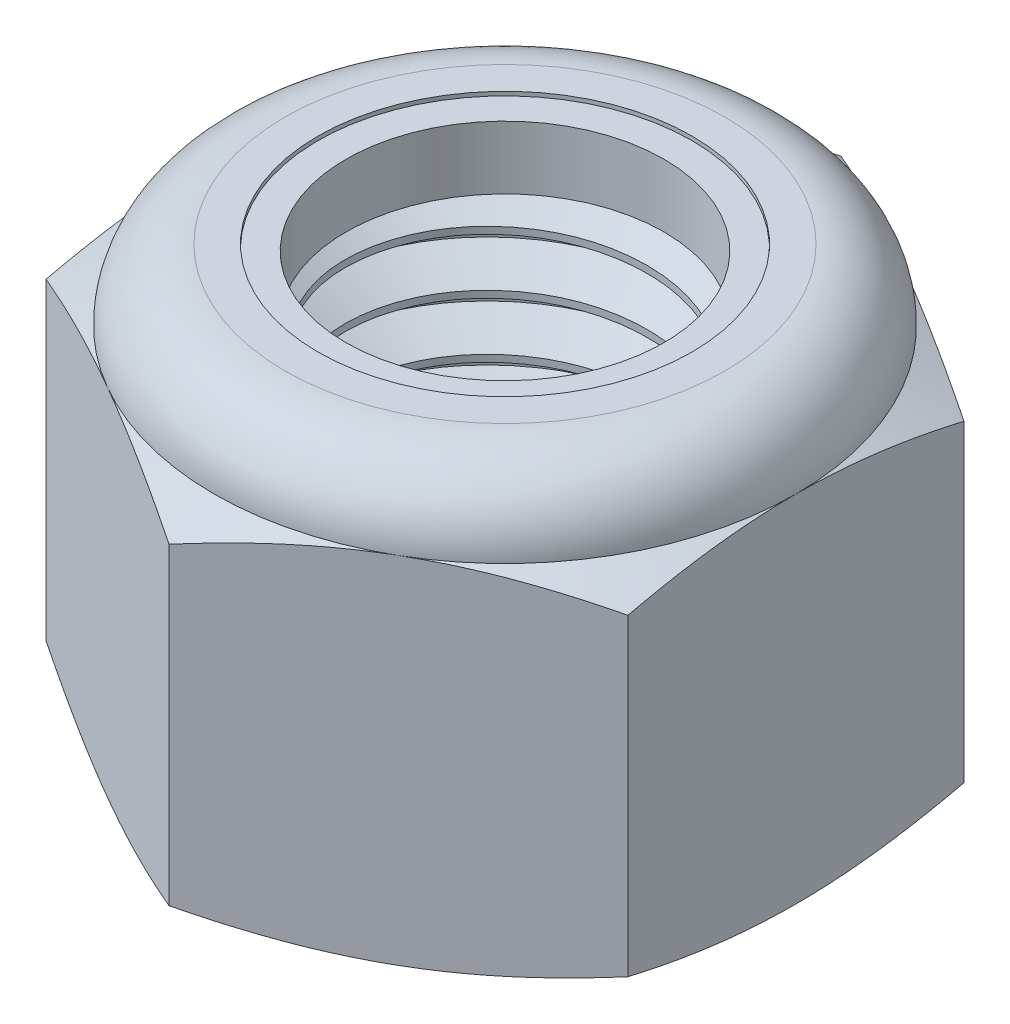
SolidWorks part; units mm, degrees
note: '?' marks a value the reader was unsure of.
material "Plain Carbon Steel"
ref_plane "Front" through (0, 0, 0) normal (0, 0, 1) x (1, 0, 0)
ref_plane "Top" through (0, 0, 0) normal (0, 1, 0) x (1, 0, 0)
ref_plane "Right" through (0, 0, 0) normal (1, 0, 0) x (0, 0, -1)
sketch "Sketch8" plane through (0, 0, 0) normal (1, 0, 0) x (0, 0, -1)
  line L0 (0, 0) -> (0, 16.2719) construction
  line L1 (11.1125, 0) -> (-11.1125, 0) construction
  line L2 (-7.1437, 16.2719) -> (7.1437, 16.2719) construction
  line L3 (7.1437, 16.2719) -> (7.1438, 14.1552) construction
sketch "Sketch1" plane through (0, 0, 0) normal (0, 1, 0) x (1, 0, 0)
  line L1 (0, 12.8316) -> (-11.1125, 6.4158)
  line L2 (-11.1125, 6.4158) -> (-11.1125, -6.4158)
  line L3 (-11.1125, -6.4158) -> (0, -12.8316)
  line L4 (0, -12.8316) -> (11.1125, -6.4158)
  line L5 (11.1125, -6.4158) -> (11.1125, 6.4158)
  line L6 (11.1125, 6.4158) -> (0, 12.8316)
  circle A0 centre (0, 0) radius 11.1125 construction
  circle A1 centre (0, 0) radius 7.1437
extrude "Extrude1" add sketch "Sketch1" along normal up to vertex (16.2719 mm away) up to point (0, 16.2719, 0)
sketch "Sketch5" plane through (0, 0, 0) normal (1, 0, 0) x (0, 0, -1)
  line L0 (0, 0) -> (11.1125, 0)
  line L1 (11.1125, 0) -> (12.8316, 0.8016)
  line L2 (12.8316, 0.8016) -> (12.8316, 12.7583)
  line L3 (12.8316, 12.7583) -> (11.1125, 13.5599)
  line L4 (8.4005, 16.2719) -> (8.4005, 17.5419)
  line L5 (8.4005, 17.5419) -> (14.1016, 17.5419)
  line L6 (14.1016, 17.5419) -> (14.1016, -1.27)
  line L7 (14.1016, -1.27) -> (0, -1.27)
  line L8 (0, -1.27) -> (0, 0)
  line L9 (11.1125, 13.5599) -> (11.1125, 0) construction
  line L12 (12.8316, 16.2719) -> (12.8316, 0) construction
  line L13 (12.8316, 8.1359) -> (14.1016, 8.1359) construction
  line L15 (0, 0) -> (0, 17.5419) construction
  line L18 (11.1125, 0) -> (-11.1125, 0) construction
  line L19 (6.4158, 16.2719) -> (12.8316, 16.2719) construction
  line L20 (0, 17.5419) -> (8.4005, 17.5419) construction
  line L21 (6.4158, 0) -> (12.8316, 0) construction
  arc A0 (11.1125, 13.5599) -> (8.4005, 16.2719) centre (8.4005, 13.5599) ccw
  dimension "D1" = 25
  dimension "D2" = 1.27
  dimension "D4" = 2.712
revolve "Cut-Revolve3" cut sketch "Sketch5" angle 360 about L15
sketch "Sketch4" plane through (0, 0, 0) normal (1, 0, 0) x (0, 0, -1)
  line L0 (0, 13.5599) -> (7.8581, 13.5599)
  line L1 (7.8581, 13.5599) -> (0, 9.8956)
  line L3 (0, 3.6643) -> (7.8581, 0)
  line L4 (7.8581, 0) -> (0, 0)
  line L5 (0, 0) -> (0, 13.5599) construction
  line L10 (0, 0) -> (0, 16.2719) construction
  line L11 (0, 3.6643) -> (0, 0)
  line L12 (0, 13.5599) -> (0, 9.8956)
  line L13 (9.6237, 13.5599) -> (0, 13.5599) construction
  dimension "D1" = 25
  dimension "D2" = 15.7162
sketch "Sketch6" plane through (0, 0, 0) normal (1, 0, 0) x (0, 0, -1)
  line L0 (0, 13.5599) -> (10.9601, 13.5599)
  line L1 (8.4005, 16.1195) -> (4.2003, 16.1195)
  line L2 (0, 17.5419) -> (0, 13.5599)
  line L3 (4.2003, 17.5419) -> (0, 17.5419)
  line L4 (0, 17.5419) -> (8.4005, 17.5419) construction
  line L5 (0, 0) -> (0, 17.5419) construction
  line L6 (0, 17.5419) -> (0, 0) construction
  line L7 (4.2003, 16.1195) -> (4.2003, 17.5419)
  line L8 (8.4005, 16.2719) -> (8.4005, 16.1195) construction
  line L9 (4.2003, 16.1195) -> (0, 16.1195) construction
  line L10 (0, 16.1195) -> (0, 9.8956) construction
  arc A0 (10.9601, 13.5599) -> (8.4005, 16.1195) centre (8.4005, 13.5599) ccw
  arc A1 (11.1125, 13.5599) -> (8.4005, 16.2719) centre (8.4005, 13.5599) ccw construction
  dimension "D1" = 0.1524
revolve "Cut-Revolve4" cut sketch "Sketch6" angle 360 about L6
revolve "Cut-Revolve2" cut sketch "Sketch4" angle 360 about L5
sketch "Sketch7" plane through (0, 0, 0) normal (1, 0, 0) x (0, 0, -1)
  line L0 (6.0722, 13.6361) -> (10.8827, 13.6361)
  line L1 (8.4005, 16.0433) -> (6.0722, 16.0433)
  line L2 (6.0722, 16.0433) -> (6.0722, 13.6361)
  line L3 (6.0722, 13.6361) -> (0, 13.6361) construction
  line L4 (0, 13.6361) -> (0, 16.0433) construction
  line L5 (0, 16.0433) -> (6.0722, 16.0433) construction
  line L6 (6.0722, 13.6361) -> (6.0722, 13.5599) construction
  line L7 (0, 13.5599) -> (10.9601, 13.5599) construction
  line L8 (8.4005, 16.0433) -> (8.4005, 16.1195) construction
  arc A0 (10.8827, 13.6361) -> (8.4005, 16.0433) centre (8.4005, 13.5599) ccw
  arc A2 (10.9601, 13.5599) -> (8.4005, 16.1195) centre (8.4005, 13.5599) ccw construction
  dimension "D1" = 0.0762
  dimension "D2" = 12.1444
revolve "Revolve2" add sketch "Sketch7" angle 360 about L4
sketch "Sketch2" plane through (0, 0, 0) normal (1, 0, 0) x (0, 0, -1)
  line L0 (-7.1437, 0) -> (-7.1437, 13.5599) construction
  line L1 (0, 0) -> (7.1437, 0)
  line L2 (0, 0) -> (0, 13.5599)
  line L3 (0, 13.5599) -> (7.1437, 13.5599)
  line L4 (7.1437, 0) -> (7.1437, 13.5599)
  line L6 (9.6237, 13.5599) -> (11.1125, 13.5599) construction
  line L7 (0, -7.1437) -> (0, 0) construction
revolve "Revolve1" add sketch "Sketch2" angle 360 about L7
sketch "Sketch9" plane through (0, 0, 0) normal (1, 0, 0) x (0, 0, -1)
  line L0 (7.3729, 15.5443) -> (7.3729, 13.4276) construction
  line L1 (7.3729, 13.4276) -> (5.5398, 14.4859) construction
  line L2 (5.5398, 14.4859) -> (7.3729, 15.5443) construction
  line L3 (5.7689, 14.6182) -> (5.7689, 14.3536) construction
  line L4 (7.1437, 15.412) -> (7.1437, 13.5599) construction
  line L5 (5.5398, 14.4859) -> (5.7689, 14.4859) construction
  line L6 (7.1437, 14.4859) -> (7.3729, 14.4859) construction
  line L7 (7.2583, 14.4859) -> (7.2583, 15.4781) construction
  line L8 (7.3729, 13.4276) -> (7.2583, 15.4781)
  line L9 (7.2583, 15.4781) -> (5.7689, 14.6182)
  line L10 (5.7689, 14.6182) -> (5.7689, 14.3536)
  line L11 (5.7689, 14.3536) -> (7.3729, 13.4276)
  dimension "D1" = 2.1167
  dimension "D2" = 0.2646
sketch "Sketch10" plane through (0, 13.5599, 0) normal (0, 1, 0) x (1, 0, 0)
  circle A1 centre (0, 0) radius 7.1438
  circle A2 centre (0, 0) radius 7.1438
  dimension "D1" = 0
curve "Helix/Spiral1" pitch 2.1167 height 18.3885 turns 8.6875
sweep "Cut-Sweep1" cut profiles "Sketch9" path "Helix/Spiral1" align with end faces yes
sketch "Sketch11" plane through (0, 0, 0) normal (1, 0, 0) x (0, 0, -1)
  line L0 (0, 0) -> (0, 16.2719) construction
  line L1 (11.1125, 0) -> (-11.1125, 0) construction
  line L4 (0, 16.2719) -> (0, 0) construction
  line L5 (0, 8.1359) -> (7.1437, 8.1359) construction
  line L6 (0, 0) -> (7.8581, 0)
  line L7 (0, 3.6643) -> (0, 0)
  line L8 (7.8581, 0) -> (0, 3.6643)
  dimension "D1" = 15.7162
  dimension "D2" = 25
revolve "Revolve3" add sketch "Sketch11" angle 360 about L4
sketch "Sketch12" plane through (0, 0, 0) normal (1, 0, 0) x (0, 0, -1)
  line L0 (7.8581, 13.5599) -> (0, 13.5599)
  line L1 (0, 13.5599) -> (0, 0)
  line L2 (0, 0) -> (7.8581, 0)
  line L3 (11.1125, 0) -> (-11.1125, 0) construction
  line L4 (7.8581, 0) -> (7.8581, 13.5599)
  line L5 (-7.8581, 0) -> (7.8581, 0) construction
revolve "Revolve4" add sketch "Sketch12" angle 360 about L0
combine bodies "Combine1" operation type subtract main body 136 bodies to subtract 133
ref_plane "Contact Plane 1" through (0, 0, 0) normal (0, -1, 0) x (1, 0, 0)
ref_axis "Center Axis 1" through (0, -2.1015, 0) along (0, 1, 0)?
equation "\"D4@Sketch5\"=\"Height@Sketch8\"/6"
equation "\"D1@Sketch9\"=\"Thread Pitch@Sketch8\""
equation "\"D2@Sketch9\"=\"Thread Pitch@Sketch8\"/8"
equation "\"D4@Helix/Spiral1\"=\"Thread Pitch@Sketch8\""
equation "\"D3@Helix/Spiral1\"=\"Thread Pitch@Sketch8\"+\"Height@Sketch8\""
equation "\"D2@Sketch4\"=\"Thread Dia@Sketch8\"*1.1"
equation "\"D1@Sketch11\"=\"Thread Dia@Sketch8\"*1.1"
equation "\"D2@Sketch7\"=\"Thread Dia@Sketch8\"*.85"
